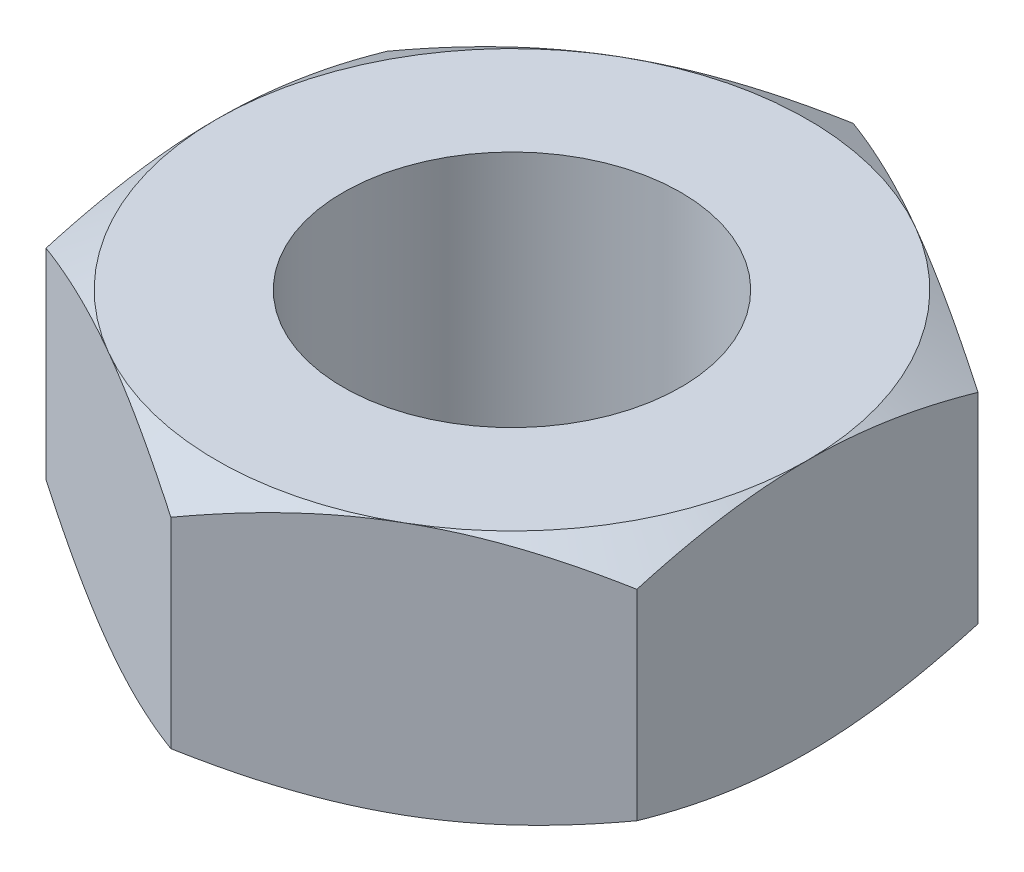
SolidWorks part; units mm, degrees
material "Wrought Stainless Steel"
ref_plane "Front Plane" through (0, 0, 0) normal (0, 0, 1) x (1, 0, 0)
ref_plane "Top Plane" through (0, 0, 0) normal (0, 1, 0) x (1, 0, 0)
ref_plane "Right Plane" through (0, 0, 0) normal (1, 0, 0) x (0, 0, -1)
sketch "Sketch1" plane through (0, 0, 0) normal (0, 1, 0) x (1, 0, 0)
  line L1 (-5.5563, 3.2079) -> (-5.5563, -3.2079)
  line L2 (-5.5563, -3.2079) -> (0, -6.4158)
  line L3 (0, -6.4158) -> (5.5562, -3.2079)
  line L4 (5.5562, -3.2079) -> (5.5562, 3.2079)
  line L5 (5.5562, 3.2079) -> (0, 6.4158)
  line L6 (0, 6.4158) -> (-5.5563, 3.2079)
  circle A0 centre (0, 0) radius 5.5563 construction
  circle A1 centre (0, 0) radius 3.175
  dimension "Thread Size" = 6.35
  dimension "Hex" = 11.1125
extrude "Boss-Extrude1" add sketch "Sketch1" along normal mid plane 4.7625
sketch "Sketch2" plane through (0, 2.3813, 0) normal (0, 1, 0) x (1, 0, 0)
  circle A0 centre (0, 0) radius 3.175 construction
  circle A1 centre (0, 0) radius 3.175
curve "Helix/Spiral1" pitch 1.27 height 6.0325 turns 4.75 parameters "Pitch"=1.27
sketch "Sketch3" plane through (0, 0, 0) normal (1, 0, 0) x (0, 0, -1)
  line L0 (2.3501, 3.0163) -> (3.175, 3.4925)
  line L1 (3.175, 3.4925) -> (3.175, 2.3813)
  line L2 (3.175, 2.3813) -> (2.3501, 2.8575)
  line L3 (2.3501, 2.8575) -> (2.3501, 3.0163)
  line L4 (2.7626, 3.2544) -> (2.7626, 2.6194) construction
  line L5 (2.3501, 2.9369) -> (3.175, 2.9369) construction
  line L6 (3.175, 2.3813) -> (-3.175, 2.3813) construction
  dimension "D1" = 60
  dimension "D2" = 0.1588
  dimension "D3" = 0.635
sweep "Sweep1" [suppressed] add profiles "Sketch3" path "Helix/Spiral1"
sketch "Sketch4" plane through (0, 2.3813, 0) normal (0, 1, 0) x (1, 0, 0)
  circle A1 centre (0, 0) radius 3.175
  circle A2 centre (0, 0) radius 3.175
  dimension "D1" = 0
extrude "Cut-Extrude1" [suppressed] cut sketch "Sketch4" along normal through all and the other way through all draft 45
sketch "Sketch5" plane through (0, 2.3813, 0) normal (0, 1, 0) x (1, 0, 0)
  circle A0 centre (0, 0) radius 5.5563 construction
  circle A1 centre (0, 0) radius 5.5563
extrude "Cut-Extrude2" cut sketch "Sketch5" against normal through all draft 60 flip side to cut
mirror "Mirror1" about plane through (0, 0, 0) normal (0, 1, 0) of "Cut-Extrude2", "Cut-Extrude1"
equation "\"D2@Sketch3\" = \"Pitch@Helix/Spiral1\"*.125"
equation "\"D3@Sketch3\" = \"Pitch@Helix/Spiral1\"*.5"
equation "\"D3@Helix/Spiral1\" = \"Height@Boss-Extrude1\"+\"Pitch@Helix/Spiral1\""
